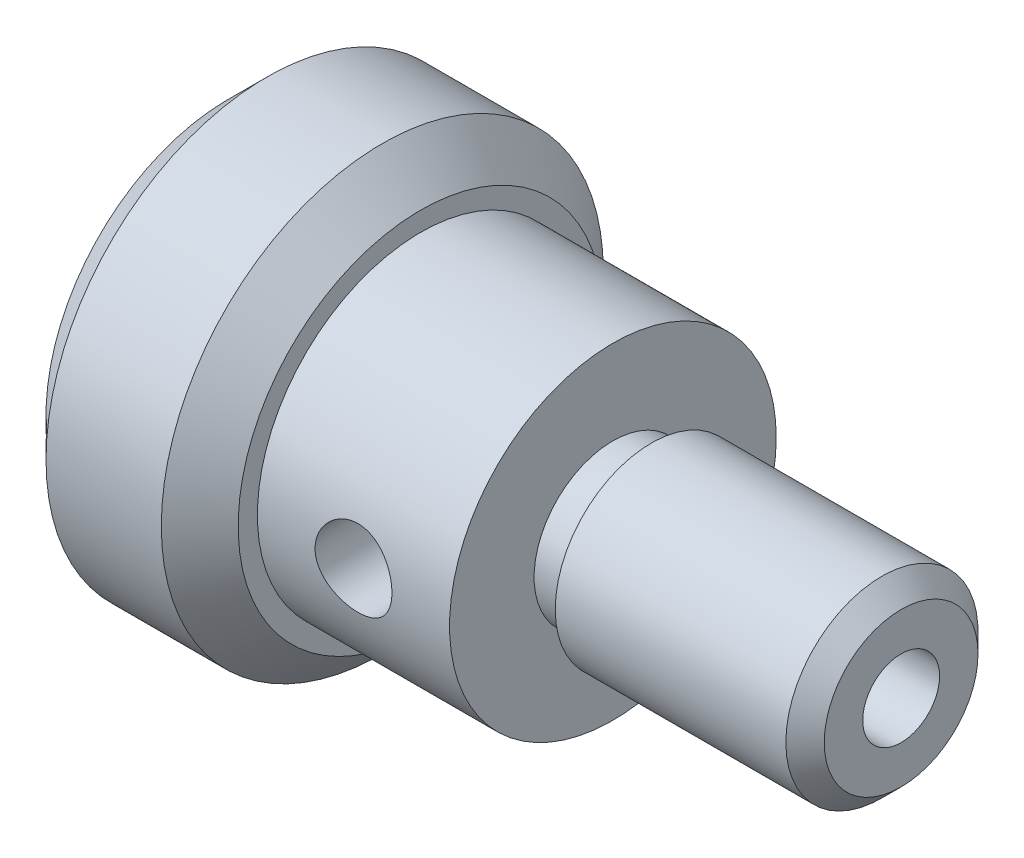
SolidWorks part; units mm, degrees
material "Q235"
ref_plane "前视基准面" through (0, 0, 0) normal (0, 0, 1) x (1, 0, 0)
ref_plane "上视基准面" through (0, 0, 0) normal (0, 1, 0) x (1, 0, 0)
ref_plane "右视基准面" through (0, 0, 0) normal (1, 0, 0) x (0, 0, -1)
ref_axis "基准轴1" through (88.99, 0, 0) along (-1, 0, 0)
sketch "草图1" plane through (0, 0, 0) normal (1, 0, 0) x (0, 0, -1)
  circle A0 centre (0, 0) radius 11.5
extrude "凸台-拉伸1" add sketch "草图1" along normal blind 10
chamfer "倒角1" distance 2 angle 45 1 edges at (0, 0, -11.5)
cosmetic thread "装饰螺纹线1" parameters "D1"=6, "D2"=20.587
chamfer "倒角2" distance 2 angle 45 1 edges at (10, 0, -11.5)
sketch "草图2" plane through (10, 0, 0) normal (1, 0, 0) x (0, 0, -1)
  circle A0 centre (0, 0) radius 8.5
extrude "凸台-拉伸2" add sketch "草图2" along normal blind 10
sketch "草图3" plane through (20, 0, 0) normal (1, 0, 0) x (0, 0, -1)
  circle A0 centre (0, 0) radius 4.1
extrude "凸台-拉伸3" add sketch "草图3" along normal blind 2
sketch "草图4" plane through (22, 0, 0) normal (1, 0, 0) x (0, 0, -1)
  circle A0 centre (0, 0) radius 5
extrude "凸台-拉伸4" add sketch "草图4" along normal blind 13
chamfer "倒角3" distance 1 angle 45 1 edges at (35, 0, -5)
sketch "草图5" plane through (0, 0, 0) normal (0, 0, 1) x (1, 0, 0)
  circle A0 centre (15, 0) radius 2
  dimension "D1" = 4
  dimension "D2" = 15
extrude "切除-拉伸1" cut sketch "草图5" against normal through all both and the other way through all
sketch "草图6" plane through (35, 0, 0) normal (1, 0, 0) x (0, 0, -1)
  circle A0 centre (0, 0) radius 2
  dimension "D1" = 4
extrude "切除-拉伸2" cut sketch "草图6" against normal blind 23 and the other way through all
